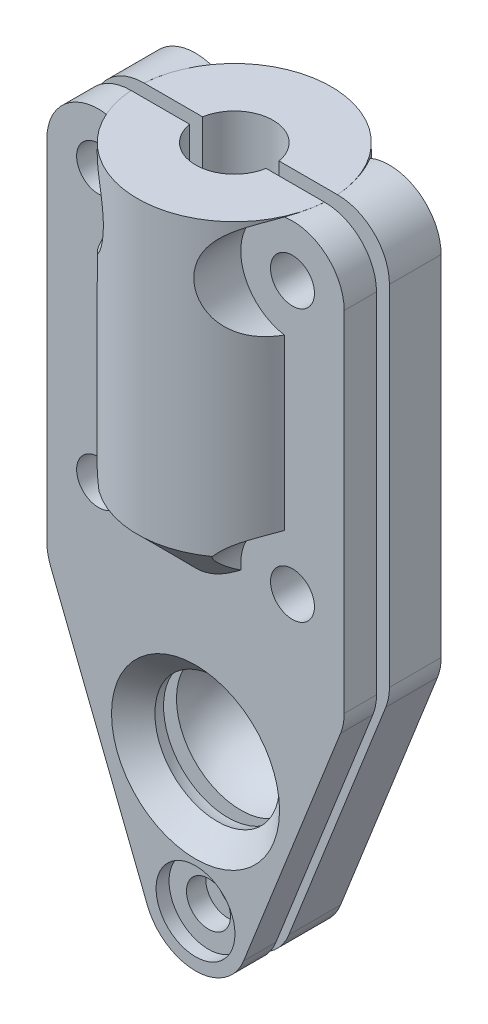
SolidWorks part; units mm, degrees
ref_plane "Front Plane" through (0, 0, 0) normal (0, 0, 1) x (1, 0, 0)
ref_plane "Top Plane" through (0, 0, 0) normal (0, 1, 0) x (1, 0, 0)
ref_plane "Right Plane" through (0, 0, 0) normal (1, 0, 0) x (0, 0, -1)
sketch "Sketch2" plane through (0, 0, 0) normal (0, 1, 0) x (1, 0, 0)
  circle A0 centre (0, 0) radius 7.5
  dimension "D1" = 15
extrude "Boss-Extrude1" add sketch "Sketch2" along normal blind 40
sketch "Sketch4" plane through (0, 0, 0) normal (0, 0, 1) x (1, 0, 0)
  circle A0 centre (0, 1) radius 7.5664
  dimension "D1" = 1
extrude "Boss-Extrude2" add sketch "Sketch4" along normal blind 3 and the other way blind 4.5
sketch "Sketch8" plane through (0, 0, 0) normal (0, 0, 1) x (1, 0, 0)
  line L0 (7.5, 2) -> (7.5, 40) construction
  line L1 (-7.5, 40) -> (-7.5, 2) construction
  line L2 (7.5, 40) -> (-7.5, 40) construction
  circle A0 centre (7.5, 36) radius 4
  circle A1 centre (7.5, 9) radius 4
  circle A2 centre (-7.5, 36) radius 4
  circle A3 centre (-7.5, 9) radius 4
  circle A4 centre (0, -10) radius 4
  dimension "D1" = 8
  dimension "D4" = 10
  dimension "D2" = 4
  dimension "D3" = 9
extrude "Boss-Extrude3" add sketch "Sketch8" along normal blind 3 and the other way up to surface other way up to face at (0, -0.2392, -4.5)
sketch "Sketch19" plane through (0, 0, 0) normal (0, 0, 1) x (1, 0, 0)
  line L4 (3.7206, -11.4687) -> (11.2206, 7.5313)
  line L5 (3.7206, -11.4687) -> (-3.7206, -11.4687)
  line L6 (-3.7206, -11.4687) -> (-11.2206, 7.5313)
  line L7 (11.5, 9) -> (11.5, 36)
  line L8 (11.5, 36) -> (-11.5, 36)
  line L9 (-11.5, 36) -> (-11.5, 9)
  line L10 (-11.5, 9) -> (-11.2206, 7.5313)
  line L11 (11.2206, 7.5313) -> (11.5, 9)
  arc A0 (-6.8739, 12.9507) -> (-6.8739, 5.0493) centre (-7.5, 9) ccw construction
  arc A1 (6.8739, 32.0493) -> (6.8739, 39.9507) centre (7.5, 36) ccw construction
  arc A2 (-1.691, -6.375) -> (1.691, -6.375) centre (0, -10) ccw construction
  arc A3 (-6.8739, 39.9507) -> (-6.8739, 32.0493) centre (-7.5, 36) ccw construction
  arc A7 (6.8739, 5.0493) -> (6.8739, 12.9507) centre (7.5, 9) ccw construction
extrude "Boss-Extrude4" add sketch "Sketch19" along normal up to surface (3 mm away) and the other way up to surface (4.5 mm away) up to face at (0, -2.4195, 3) other way up to face at (0, 1.6777, -4.5)
sketch "Sketch5" plane through (0, 0, 0) normal (0, 0, 1) x (1, 0, 0)
  line L0 (-5, 0) -> (5, 0)
  arc A0 (-5, 0) -> (5, 0) centre (0, 0) ccw
  point P3 (0, 0)
  dimension "D1" = 10
revolve "Cut-Revolve1" cut sketch "Sketch5" angle 360 about L0
sketch "Sketch9" plane through (0, 0, 3) normal (0, 0, 1) x (1, 0, 0)
  circle A0 centre (7.5, 36) radius 1.7
  circle A1 centre (7.5, 15) radius 1.7
  circle A2 centre (-7.5, 15) radius 1.7
  circle A3 centre (-7.5, 36) radius 1.7
  circle A4 centre (0, -10) radius 1.7
  point P5 (0, 0)
  dimension "D1" = 3.4
  dimension "D2" = 15
extrude "Cut-Extrude6" cut sketch "Sketch9" against normal through all both and the other way through all
sketch "Sketch10" plane through (0, 0, 3) normal (0, 0, 1) x (1, 0, 0)
  circle A0 centre (7.5, 36) radius 4
  circle A1 centre (-7.5, 36) radius 4
  circle A2 centre (-7.5, 15) radius 4
  circle A3 centre (7.5, 15) radius 4
  dimension "D1" = 8
extrude "Cut-Extrude7" cut sketch "Sketch10" along normal through all
sketch "Sketch12" plane through (0, 0, 0) normal (0, 0, 1) x (1, 0, 0)
  circle A0 centre (7.5, 36) radius 1.95
  circle A1 centre (-7.5, 36) radius 1.95
  circle A2 centre (-7.5, 15) radius 1.95
  circle A3 centre (7.5, 15) radius 1.95
  circle A4 centre (0, -10) radius 1.95
  dimension "D1" = 3.9
extrude "Cut-Extrude9" cut sketch "Sketch12" against normal blind 10
sketch "Sketch14" plane through (0, 0, -4.5) normal (0, 0, -1) x (-1, 0, 0)
  line L1 (-7.5, -5.0493) -> (7.5, -5.0493)
  line L2 (-7.5, -5.0493) -> (-7.5, 13)
  line L3 (-7.5, 13) -> (7.5, 13)
  line L4 (7.5, -5.0493) -> (7.5, 13)
  line L5 (-7.5, -5.0493) -> (7.5, 13) construction
  line L6 (-7.5, 13) -> (7.5, -5.0493) construction
  arc A0 (-11.5, 9) -> (-11.2206, 7.5313) centre (-7.5, 9) ccw construction
extrude "Cut-Extrude14" cut sketch "Sketch14" along normal blind 10
sketch "Sketch15" plane through (0, 0, 3) normal (0, 0, 1) x (1, 0, 0)
  line L1 (-7.5, 13) -> (7.5, 13)
  line L2 (-7.5, 13) -> (-7.5, -6.5104)
  line L3 (-7.5, -6.5104) -> (7.5, -6.5104)
  line L4 (7.5, 13) -> (7.5, -6.5104)
extrude "Cut-Extrude15" cut sketch "Sketch15" along normal blind 10
chamfer "Chamfer3" distance 4.5 angle 45 2 edges at (0, 13, -7.5) (0, 13, 7.5)
chamfer "Chamfer1" distance 2.5 angle 45 1 edges at (4, 0, 3) first distance on face at (4, 0, 3)
sketch "Sketch3" plane through (0, 40, 0) normal (0, 1, 0) x (1, 0, 0)
  circle A0 centre (0, 0) radius 3
  dimension "D1" = 6
extrude "Cut-Extrude3" cut sketch "Sketch3" against normal blind 25.5
sketch "Sketch16" plane through (0, 0, 3) normal (0, 0, 1) x (1, 0, 0)
  circle A0 centre (0, -10) radius 3.05
  dimension "D1" = 6.1
extrude "Cut-Extrude16" cut sketch "Sketch16" against normal blind 1
sketch "Sketch23" plane through (0, 0, -4.5) normal (0, 0, -1) x (-1, 0, 0)
  line L1 (-10.9064, 15) -> (-9.2032, 12.05)
  line L2 (-9.2032, 12.05) -> (-5.7968, 12.05)
  line L3 (-5.7968, 12.05) -> (-4.0936, 15)
  line L4 (-4.0936, 15) -> (-5.7968, 17.95)
  line L5 (-5.7968, 17.95) -> (-9.2032, 17.95)
  line L6 (-9.2032, 17.95) -> (-10.9064, 15)
  line L7 (4.0936, 15) -> (5.7968, 12.05)
  line L8 (5.7968, 12.05) -> (9.2032, 12.05)
  line L9 (9.2032, 12.05) -> (10.9064, 15)
  line L10 (10.9064, 15) -> (9.2032, 17.95)
  line L11 (9.2032, 17.95) -> (5.7968, 17.95)
  line L12 (5.7968, 17.95) -> (4.0936, 15)
  line L13 (-10.9064, 36) -> (-9.2032, 33.05)
  line L14 (-9.2032, 33.05) -> (-5.7968, 33.05)
  line L15 (-5.7968, 33.05) -> (-4.0936, 36)
  line L16 (-4.0936, 36) -> (-5.7968, 38.95)
  line L17 (-5.7968, 38.95) -> (-9.2032, 38.95)
  line L18 (-9.2032, 38.95) -> (-10.9064, 36)
  line L19 (10.9064, 36) -> (9.2032, 38.95)
  line L20 (9.2032, 38.95) -> (5.7968, 38.95)
  line L21 (5.7968, 38.95) -> (4.0936, 36)
  line L22 (4.0936, 36) -> (5.7968, 33.05)
  line L23 (5.7968, 33.05) -> (9.2032, 33.05)
  line L24 (9.2032, 33.05) -> (10.9064, 36)
  line L25 (-3.4064, -10) -> (-1.7032, -12.95)
  line L26 (-1.7032, -12.95) -> (1.7032, -12.95)
  line L27 (1.7032, -12.95) -> (3.4064, -10)
  line L28 (3.4064, -10) -> (1.7032, -7.05)
  line L29 (1.7032, -7.05) -> (-1.7032, -7.05)
  line L30 (-1.7032, -7.05) -> (-3.4064, -10)
  circle A0 centre (-7.5, 15) radius 2.95 construction
  circle A1 centre (7.5, 15) radius 2.95 construction
  circle A2 centre (-7.5, 36) radius 2.95 construction
  circle A3 centre (7.5, 36) radius 2.95 construction
  circle A4 centre (0, -10) radius 2.95 construction
  dimension "D1" = 5.9
extrude "Cut-Extrude18" cut sketch "Sketch23" against normal blind 2.2 and the other way through all
sketch "Sketch21" plane through (0, 0, 0) normal (0, 1, 0) x (1, 0, 0)
  line L1 (-15, -0.5) -> (15, -0.5)
  line L2 (-15, -0.5) -> (-15, 0.5)
  line L3 (-15, 0.5) -> (15, 0.5)
  line L4 (15, -0.5) -> (15, 0.5)
  line L5 (-15, -0.5) -> (15, 0.5) construction
  line L6 (-15, 0.5) -> (15, -0.5) construction
  point P0 (0, 0)
  dimension "D1" = 1
  dimension "D2" = 30
extrude "Cut-Extrude17" cut sketch "Sketch21" against normal through all both and the other way through all
